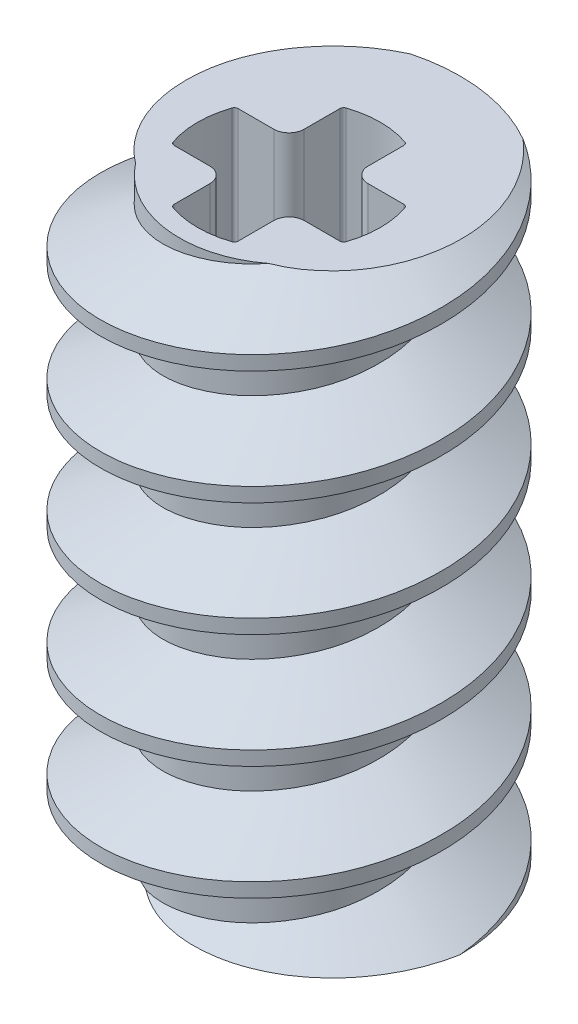
SolidWorks part; units mm, degrees
ref_plane "Front Plane" through (0, 0, 0) normal (0, 0, 1) x (1, 0, 0)
ref_plane "Top Plane" through (0, 0, 0) normal (0, 1, 0) x (1, 0, 0)
ref_plane "Right Plane" through (0, 0, 0) normal (1, 0, 0) x (0, 0, -1)
sketch "Sketch1" plane through (0, 0, 0) normal (0, 1, 0) x (1, 0, 0)
  circle A0 centre (0, 0) radius 4.5
  dimension "D1" = 9
extrude "Boss-Extrude1" add sketch "Sketch1" along normal mid plane 15.5
thread "Thread2" pitch 3 method cut profile "Thread Profile2" start angle 0, offset 6, length 0, pitch 3, diameter 9
ref_plane "Plane2" through (4.5, -13.75, 0) normal (0, 0, 1) x (1, 0, 0)
sketch "Thread Profile2" plane through (4.5, -13.75, 0) normal (0, 0, 1) x (1, 0, 0)
  line L0 (0, 0) -> (0, 3) construction
  line L11 (0, 0) -> (0, 2.625)
  line L12 (0, 2.625) -> (-1.6238, 1.6875)
  line L13 (-1.6238, 1.6875) -> (-1.6238, 0.9375)
  line L15 (-1.6238, 0.9375) -> (0, 0)
  line L17 (-1.6238, 1.3125) -> (0, 1.3125) construction
  point P2 (0, 0)
  dimension "Pitch" = 3
  dimension "Profile_Angle" = 60
  dimension "Profile_Land" = 0.75
  dimension "Profile_Height" = 1.6238
sketch "Sketch2" plane through (0, 7.75, 0) normal (0, 1, 0) x (1, 0, 0)
  line L0 (-0.84, 1.24) -> (-0.84, 2.1777)
  line L1 (-0.84, -2.2482) -> (0.84, -2.2482) construction
  line L2 (-0.84, -2.1777) -> (-0.84, -1.24)
  line L3 (-0.84, 2.2482) -> (0.84, 2.2482) construction
  line L4 (0.84, -2.1777) -> (0.84, -1.24)
  line L5 (-0.84, -2.2482) -> (0.84, 2.2482) construction
  line L6 (-0.84, 2.2482) -> (0.84, -2.2482) construction
  line L7 (2.1777, 0.84) -> (1.24, 0.84)
  line L8 (2.2482, 0.84) -> (2.2482, -0.84) construction
  line L9 (2.1777, -0.84) -> (1.24, -0.84)
  line L10 (-2.2482, 0.84) -> (-2.2482, -0.84) construction
  line L11 (2.2482, 0.84) -> (-2.2482, -0.84) construction
  line L12 (2.2482, -0.84) -> (-2.2482, 0.84) construction
  line L13 (-1.24, -0.84) -> (-2.1777, -0.84)
  line L14 (0.84, 1.24) -> (0.84, 2.1777)
  line L15 (-1.24, 0.84) -> (-2.1777, 0.84)
  arc A0 (-2.2724, 0.7722) -> (-2.2724, -0.7722) centre (0, 0) ccw
  arc A1 (0.7722, 2.2724) -> (-0.7722, 2.2724) centre (0, 0) ccw
  arc A2 (2.2724, -0.7722) -> (2.2724, 0.7722) centre (0, 0) ccw
  arc A3 (-0.7722, -2.2724) -> (0.7722, -2.2724) centre (0, 0) ccw
  arc A4 (-0.84, -1.24) -> (-1.24, -0.84) centre (-1.24, -1.24) ccw
  arc A5 (1.24, -0.84) -> (0.84, -1.24) centre (1.24, -1.24) ccw
  arc A6 (0.84, 1.24) -> (1.24, 0.84) centre (1.24, 1.24) ccw
  arc A7 (-0.84, 1.24) -> (-1.24, 0.84) centre (-1.24, 1.24) cw
  arc A8 (-2.1777, 0.84) -> (-2.2724, 0.7722) centre (-2.1777, 0.74) ccw
  arc A9 (-2.1777, -0.84) -> (-2.2724, -0.7722) centre (-2.1777, -0.74) cw
  arc A10 (-0.7722, -2.2724) -> (-0.84, -2.1777) centre (-0.74, -2.1777) cw
  arc A11 (0.7722, -2.2724) -> (0.84, -2.1777) centre (0.74, -2.1777) ccw
  arc A12 (2.2724, -0.7722) -> (2.1777, -0.84) centre (2.1777, -0.74) cw
  arc A13 (2.1777, 0.84) -> (2.2724, 0.7722) centre (2.1777, 0.74) cw
  arc A14 (0.7722, 2.2724) -> (0.84, 2.1777) centre (0.74, 2.1777) cw
  arc A15 (-0.84, 2.1777) -> (-0.7722, 2.2724) centre (-0.74, 2.1777) cw
  point P16 (-0.84, -0.84)
  point P23 (-0.84, 0.84)
  dimension "D1" = 4.8
  dimension "D4" = 0.4
  dimension "D5" = 0.1
  dimension "D2" = 1.68
  dimension "D3" = 1.68
extrude "Cut-Extrude1" cut sketch "Sketch2" against normal through all
